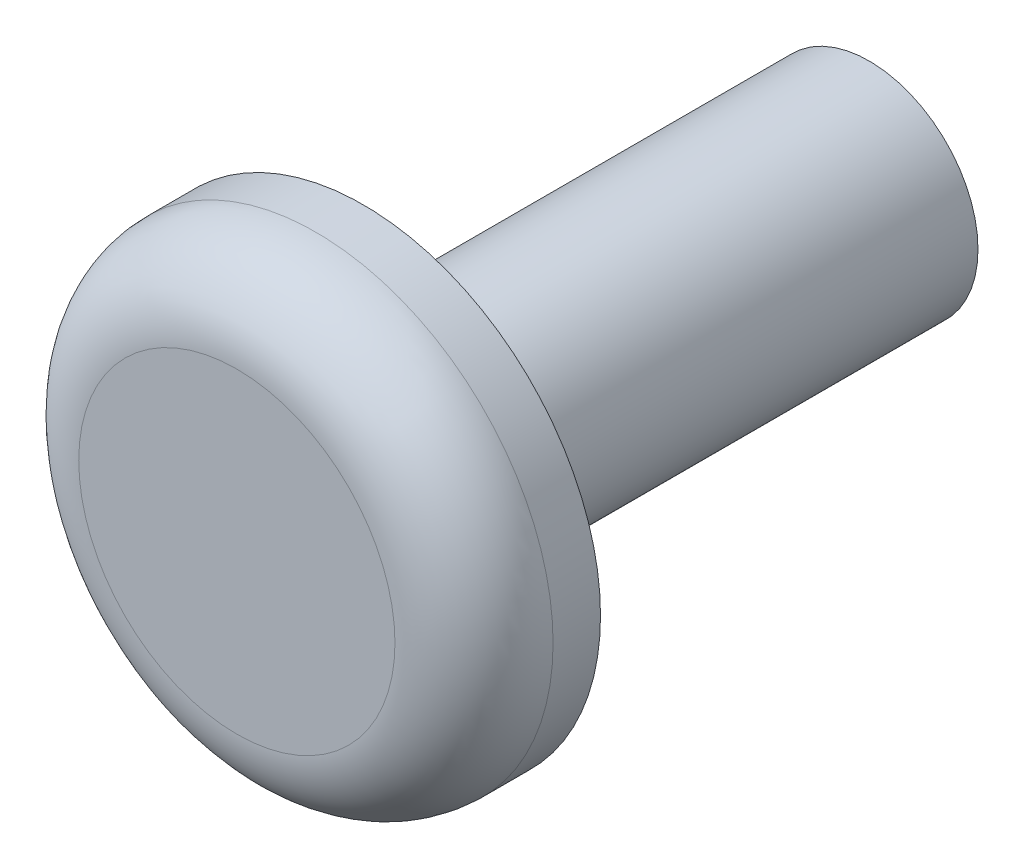
SolidWorks part; units mm, degrees
ref_plane "Front Plane" through (0, 0, 0) normal (0, 0, 1) x (1, 0, 0)
ref_plane "Top Plane" through (0, 0, 0) normal (0, 1, 0) x (1, 0, 0)
ref_plane "Right Plane" through (0, 0, 0) normal (1, 0, 0) x (0, 0, -1)
sketch "Sketch1" plane through (0, 0, 0) normal (0, 0, 1) x (1, 0, 0)
  circle A0 centre (0, 0) radius 3.4375
  dimension "D1" = 6.875
extrude "Boss-Extrude1" add sketch "Sketch1" along normal blind 16
sketch "Sketch2" plane through (0, 0, 16) normal (0, 0, 1) x (1, 0, 0)
  circle A0 centre (0, 0) radius 7.5
  dimension "D1" = 15
extrude "Boss-Extrude2" add sketch "Sketch2" along normal blind 4
sketch "Sketch3" plane through (0, 0, 0) normal (0, 0, -1) x (-1, 0, 0)
  circle A0 centre (0, 0) radius 1.5
extrude "Cut-Extrude1" cut sketch "Sketch3" against normal blind 5
chamfer "Chamfer1" distance 0.2 distance2 1 1 edges at (-1.5, 0, 0) first distance on face at (-1.5, 0, 0)
fillet "Fillet1" radius 2.5 1 edges at (7.5, 0, 20)
